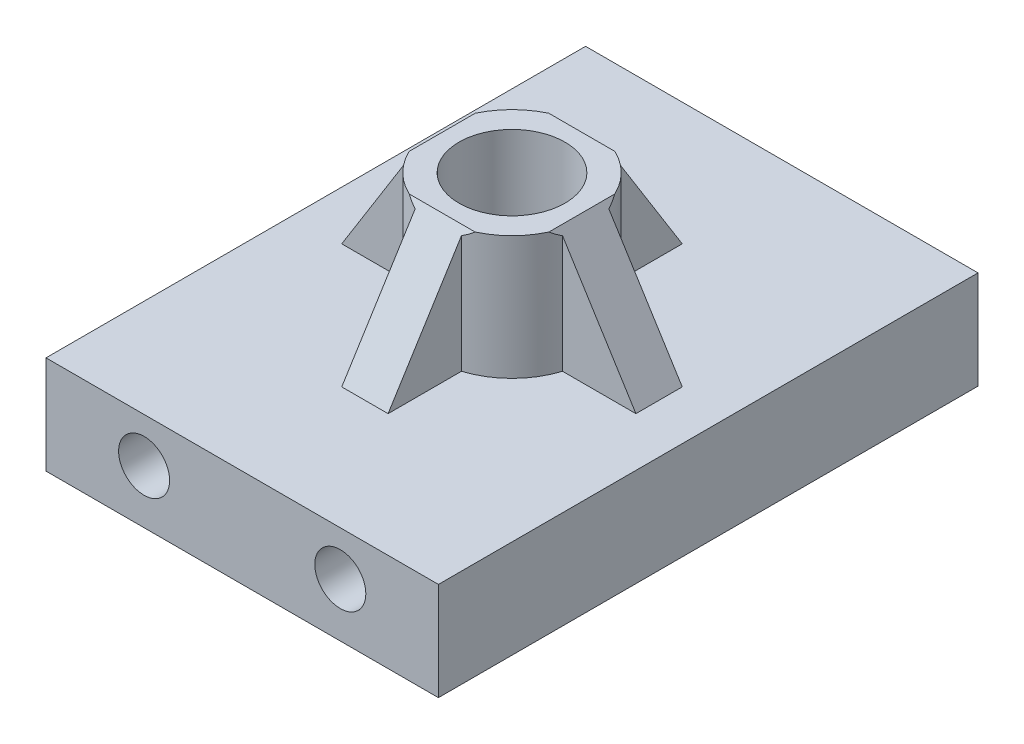
SolidWorks part; units mm, degrees
ref_plane "Front Plane" through (0, 0, 0) normal (0, 0, 1) x (1, 0, 0)
ref_plane "Top Plane" through (0, 0, 0) normal (0, 1, 0) x (1, 0, 0)
ref_plane "Right Plane" through (0, 0, 0) normal (1, 0, 0) x (0, 0, -1)
sketch "Sketch1" plane through (0, 0, 0) normal (0, 0, 1) x (1, 0, 0)
  line L1 (0, 0) -> (25.4, 0)
  line L2 (0, 0) -> (0, 6.35)
  line L3 (0, 6.35) -> (25.4, 6.35)
  line L4 (25.4, 0) -> (25.4, 6.35)
  dimension "D1" = 25.4
  dimension "D2" = 6.35
extrude "Boss-Extrude1" add sketch "Sketch1" along normal blind 34.925
sketch "Sketch2" plane through (0, 0, 34.925) normal (0, 0, 1) x (1, 0, 0)
  line L0 (0, 6.35) -> (0, 0) construction
  line L1 (25.4, 6.35) -> (0, 6.35) construction
  circle A0 centre (6.35, 3.4721) radius 1.651
  circle A1 centre (19.05, 3.4721) radius 1.651
  point P5 (0, 3.175)
  point P6 (12.7, 6.35)
  dimension "D1" = 3.302
  dimension "D2" = 12.7
  dimension "D3" = 6.35
extrude "Cut-Extrude1" cut sketch "Sketch2" against normal blind 15
ref_plane "Plane1" through (0, 0, 17.4625) normal (0, 0, 1) x (1, 0, 0)
mirror "Mirror1" about plane through (0, 0, 17.4625) normal (0, 0, 1) of "Cut-Extrude1"
sketch "Sketch3" plane through (0, 6.35, 0) normal (0, 1, 0) x (1, 0, 0)
  line L0 (25.4, 0) -> (0, 0) construction
  line L1 (0, -34.925) -> (0, 0) construction
  circle A0 centre (12.7, -17.4625) radius 3.429
  point P2 (12.7, 0)
  point P3 (0, -17.4625)
  dimension "D1" = 6.858
extrude "Cut-Extrude2" cut sketch "Sketch3" against normal through all
sketch "Sketch4" plane through (0, 6.35, 0) normal (0, 1, 0) x (1, 0, 0)
  circle A0 centre (12.7, -17.4625) radius 3.429
  circle A1 centre (12.7, -17.4625) radius 5
  circle A2 centre (12.7, -17.4625) radius 3.429 construction
  dimension "D1" = 10
extrude "Boss-Extrude2" add sketch "Sketch4" along normal blind 8
sketch "Sketch5" plane through (0, 6.35, 0) normal (0, 1, 0) x (1, 0, 0)
  line L1 (11.2, -6.6928) -> (14.2, -6.6928)
  line L2 (11.2, -6.6928) -> (11.2, -12.6928)
  line L3 (11.2, -12.6928) -> (14.2, -12.6928)
  line L4 (14.2, -6.6928) -> (14.2, -12.6928)
  circle A0 centre (12.7, -17.4625) radius 5 construction
  point P4 (12.7, -17.4625)
  point P5 (12.7, -6.6928)
  dimension "D1" = 3
  dimension "D2" = 6
extrude "Boss-Extrude3" add sketch "Sketch5" along normal up to surface (8 mm away) up to face at (12.7, 14.35, 22.4625)
chamfer "Chamfer1" distance 10 angle 32 1 edges at (12.7, 14.35, 6.6928) first distance on face at (12.7, 10.35, 6.6928)
pattern_circular "CirPattern1" count 4 over 360 about axis through (12.7, 14.35, 17.4625) along (0, -1, 0) of "Boss-Extrude3", "Chamfer1" reverse direction yes
